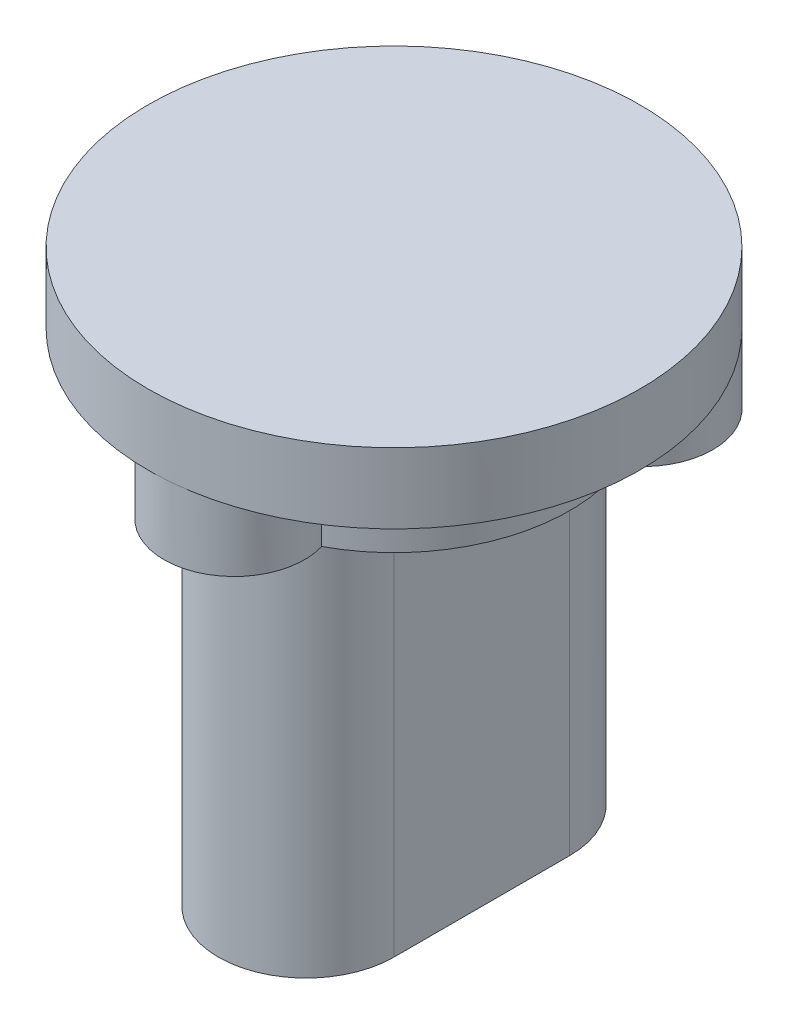
SolidWorks part; units mm, degrees
ref_plane "Front Plane" through (0, 0, 0) normal (0, 0, 1) x (1, 0, 0)
ref_plane "Top Plane" through (0, 0, 0) normal (0, 1, 0) x (1, 0, 0)
ref_plane "Right Plane" through (0, 0, 0) normal (1, 0, 0) x (0, 0, -1)
sketch "Sketch1" plane through (0, 0, 0) normal (0, 1, 0) x (1, 0, 0)
  line L0 (0, 2.5) -> (0, -2.5) construction
  line L1 (2.5, 2.5) -> (2.5, -2.5)
  line L2 (-2.5, 2.5) -> (-2.5, -2.5)
  line L3 (0.4358, -4.981) -> (-4.981, 0.4358) construction
  arc A1 (2.5, 2.5) -> (-2.5, 2.5) centre (0, 2.5) ccw
  arc A2 (-2.5, -2.5) -> (2.5, -2.5) centre (0, -2.5) ccw
  circle A3 centre (3.5355, 3.5355) radius 2
  circle A4 centre (-4.981, 0.4358) radius 2
  circle A5 centre (0.4358, -4.981) radius 2
  circle A6 centre (0, 0) radius 5
  circle A7 centre (0, 0) radius 7
  point P3 (0, 0)
  point P9 (0, 5)
  point P10 (0, -5)
  point P18 (-2.2726, -2.2726)
  point P20 (0, 0)
  point P21 (0, 0)
  dimension "D3" = 2.5
  dimension "D4" = 4
  dimension "D5" = 4
  dimension "D6" = 4
  dimension "D7" = 10
  dimension "D1" = 25
  dimension "D2" = 10
  dimension "D8" = 90
  dimension "key_angle_offset" = 45
extrude "Boss-Extrude1" add sketch "Sketch1" against normal blind 13 contours L2 A2 L1 A1
extrude "Boss-Extrude2" add sketch "Sketch1<3>" against normal blind 2 contours A6 A5 | A6 A4 | A6 A3 | A6 region at (4.0819, 0, -4.0819) region at (-5.7507, 0, -0.5031) region at (0.5031, 0, 5.7507)
sketch "Sketch1<3>" plane through (0, 0, 0) normal (0, 1, 0) x (1, 0, 0) same geometry as "Sketch1"
extrude "Boss-Extrude3" add sketch "Sketch1<4>" along normal blind 2 contours A7
sketch "Sketch1<4>" plane through (0, 0, 0) normal (0, 1, 0) x (1, 0, 0) same geometry as "Sketch1"
